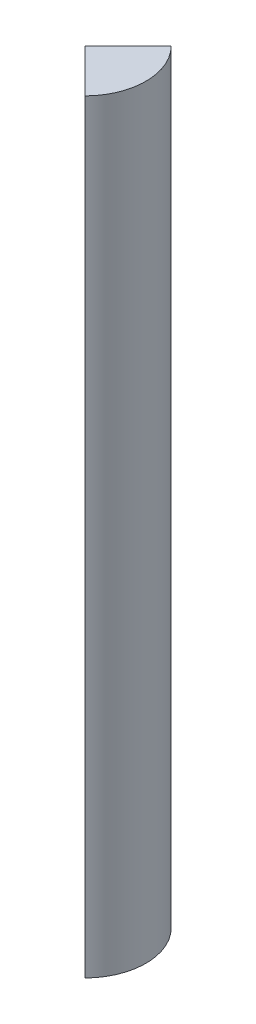
SolidWorks part; units mm, degrees
other "Markup1"
sketch "Sketch12"
ref_plane "Front Plane" through (0, 0, 0) normal (1, 0, 0) x (0, 1, 0)
ref_plane "Top Plane" through (0, 0, 0) normal (0, 0, 1) x (0, 1, 0)
ref_plane "Right Plane" through (0, 0, 0) normal (0, 1, 0) x (-1, 0, 0)
sketch "Sketch2" plane through (0, 0, 0) normal (1, 0, 0) x (0, 1, 0)
  line L0 (0, 0) -> (762, 0) construction
  line L1 (762, 0) -> (762, 78.359) construction
  line L2 (762, 78.359) -> (762, 76.2)
  line L3 (3.4018, 0) -> (0, 0)
  spline S0 degree 4 poles (0, 0) (0.0023, 0.0105) (0.0086, 0.031) (0.0277, 0.0698) (0.0612, 0.1247) (0.1053, 0.1858) (0.1923, 0.2927) (0.3229, 0.4308) (0.4903, 0.5871) (0.695, 0.7599) (0.9129, 0.9313) (1.1432, 1.102) (1.5318, 1.3747) (2.2426, 1.8346) (3.5248, 2.5796) (5.9038, 3.7977) (10.1506, 5.6937) (17.4785, 8.5235) (29.8706, 12.6463) (49.7755, 18.3188) (79.4252, 25.5145) (117.5433, 33.3386) (161.8994, 41.077) (209.5287, 48.1681) (257.2931, 54.2742) (305.159, 59.5209) (353.1026, 63.9965) (401.1066, 67.7665) (449.1572, 70.8839) (497.2431, 73.3933) (545.3551, 75.337) (593.4853, 76.7561) (641.627, 77.698) (689.7749, 78.217) (725.8875, 78.3488) (749.9625, 78.359) (762, 78.359) knots 0 0 0 0 0 0.000056 0.000112 0.000223 0.000335 0.000447 0.000828 0.00121 0.001524 0.001839 0.002269 0.002699 0.003991 0.006237 0.009973 0.016584 0.028152 0.047047 0.077827 0.124124 0.186686 0.249249 0.311812 0.374374 0.436937 0.4995 0.562062 0.624625 0.687187 0.74975 0.812312 0.874875 0.937438 1 1 1 1 1 construction
  spline S1 degree 4 poles (0, 0) (0.0023, 0.0105) (0.0086, 0.031) (0.0277, 0.0698) (0.0612, 0.1247) (0.1053, 0.1858) (0.1923, 0.2927) (0.3229, 0.4308) (0.4903, 0.5871) (0.695, 0.7599) (0.9129, 0.9313) (1.1432, 1.102) (1.5318, 1.3747) (2.2426, 1.8346) (3.5248, 2.5796) (5.9038, 3.7977) (10.1506, 5.6937) (17.4785, 8.5235) (29.8706, 12.6463) (49.7755, 18.3188) (79.4252, 25.5145) (117.5433, 33.3386) (161.8994, 41.077) (209.5287, 48.1681) (257.2931, 54.2742) (305.159, 59.5209) (353.1026, 63.9965) (401.1066, 67.7665) (449.1572, 70.8839) (497.2431, 73.3933) (545.3551, 75.337) (593.4853, 76.7561) (641.627, 77.698) (689.7749, 78.217) (725.8875, 78.3488) (749.9625, 78.359) (762, 78.359) knots 0 0 0 0 0 0.000056 0.000112 0.000223 0.000335 0.000447 0.000828 0.00121 0.001524 0.001839 0.002269 0.002699 0.003991 0.006237 0.009973 0.016584 0.028152 0.047047 0.077827 0.124124 0.186686 0.249249 0.311812 0.374374 0.436937 0.4995 0.562062 0.624625 0.687187 0.74975 0.812312 0.874875 0.937438 1 1 1 1 1
  spline S2 degree 1 poles (1.8679, -1.0827) (762, 76.2) knots 0 0 1 1 construction
  spline S3 degree 3 poles (1.8679, -1.0827) (1.9227, -1.0307) (2.0262, -0.9405) (2.3297, -0.7011) (2.7367, -0.4169) (3.1827, -0.1323) (3.5725, 0.1036) (4.1963, 0.4671) (5.1592, 0.9878) (6.879, 1.8455) (9.0976, 2.8537) (12.725, 4.3663) (17.3507, 6.113) (22.981, 8.0553) (28.6626, 9.8797) (36.2888, 12.1887) (45.8901, 14.8818) (57.4863, 17.8837) (69.1347, 20.7008) (80.8252, 23.3612) (96.4567, 26.7299) (116.0643, 30.6435) (139.6744, 34.9497) (163.347, 38.9211) (187.0706, 42.5955) (210.8364, 46.0019) (242.5718, 50.2157) (282.3174, 54.9128) (330.1041, 59.7424) (377.962, 63.8395) (425.875, 67.262) (489.8157, 70.9904) (569.8224, 74.1892) (665.8918, 76.035) (729.9659, 76.2) (762, 76.2) knots 0.000806 0.000806 0.000806 0.000806 0.001294 0.001782 0.002757 0.003609 0.004097 0.004709 0.00666 0.008612 0.012515 0.016418 0.024224 0.032031 0.039837 0.047643 0.063255 0.078868 0.09448 0.110093 0.125705 0.15693 0.188155 0.219379 0.250604 0.281829 0.313054 0.375504 0.437953 0.500403 0.562853 0.625302 0.750201 0.875101 1 1 1 1 only from (3.4018, 0) to (762, 76.2)
  dimension "D1" = 2.159
sketch "Sketch4" plane through (0, 0, 0) normal (1, 0, 0) x (0, 1, 0)
  line L0 (0, 0) -> (762, 0)
  line L1 (762, 0) -> (762, 78.359)
  spline S0 degree 4 poles (-2870.5736, 769.8211) (68.5769, -19.0817) (0.1375, -1.5402) (-0.2978, -0.4636) (0.0612, 0.1247) (0.1053, 0.1858) (0.1923, 0.2927) (0.3229, 0.4308) (0.4903, 0.5871) (0.695, 0.7599) (0.9129, 0.9313) (1.1432, 1.102) (1.5318, 1.3747) (2.2426, 1.8346) (3.5248, 2.5796) (5.9038, 3.7977) (10.1506, 5.6937) (17.4785, 8.5235) (29.8706, 12.6463) (49.7755, 18.3188) (79.4252, 25.5145) (117.5433, 33.3386) (161.8994, 41.077) (209.5287, 48.1681) (257.2931, 54.2742) (305.159, 59.5209) (353.1026, 63.9965) (401.1066, 67.7665) (449.1572, 70.8839) (497.2431, 73.3933) (545.3551, 75.337) (593.4853, 76.7561) (641.627, 77.698) (949.2491, 81.0136) (1244.9482, 66.9537) (1527.4922, 97.6231) (1819.2843, 2734.4842) knots -0.003249 -0.003249 -0.003249 -0.003249 -0.003249 0.000056 0.000112 0.000223 0.000335 0.000447 0.000828 0.00121 0.001524 0.001839 0.002269 0.002699 0.003991 0.006237 0.009973 0.016584 0.028152 0.047047 0.077827 0.124124 0.186686 0.249249 0.311812 0.374374 0.436937 0.4995 0.562062 0.624625 0.687187 0.74975 0.812312 0.874875 0.937438 2.348626 2.348626 2.348626 2.348626 2.348626 only from (0, 0) to (762, 78.359) construction
  spline S1 degree 4 poles (0, 0) (0.0023, 0.0105) (0.0086, 0.031) (0.0277, 0.0698) (0.0612, 0.1247) (0.1053, 0.1858) (0.1923, 0.2927) (0.3229, 0.4308) (0.4903, 0.5871) (0.695, 0.7599) (0.9129, 0.9313) (1.1432, 1.102) (1.5318, 1.3747) (2.2426, 1.8346) (3.5248, 2.5796) (5.9038, 3.7977) (10.1506, 5.6937) (17.4785, 8.5235) (29.8706, 12.6463) (49.7755, 18.3188) (79.4252, 25.5145) (117.5433, 33.3386) (161.8994, 41.077) (209.5287, 48.1681) (257.2931, 54.2742) (305.159, 59.5209) (353.1026, 63.9965) (401.1066, 67.7665) (449.1572, 70.8839) (497.2431, 73.3933) (545.3551, 75.337) (593.4853, 76.7561) (641.627, 77.698) (689.7749, 78.217) (725.8875, 78.3488) (749.9625, 78.359) (762, 78.359) knots 0 0 0 0 0 0.000056 0.000112 0.000223 0.000335 0.000447 0.000828 0.00121 0.001524 0.001839 0.002269 0.002699 0.003991 0.006237 0.009973 0.016584 0.028152 0.047047 0.077827 0.124124 0.186686 0.249249 0.311812 0.374374 0.436937 0.4995 0.562062 0.624625 0.687187 0.74975 0.812312 0.874875 0.937438 1 1 1 1 1
revolve "Revolve1" add sketch "Sketch4" angle 360 about L0 region at (0, 454.2197, 32.884)
sketch "Sketch5" plane through (0, 762, 0) normal (0, 1, 0) x (-1, 0, 0)
  circle A1 centre (0, 0) radius 78.359
  circle A2 centre (0, 0) radius 78.359
  dimension "D1" = 0
extrude "Boss-Extrude1" add sketch "Sketch5" along normal blind 1117.6
ref_axis "Axis1" through (0, 1879.6, 0) along (0, -1, 0)
sketch "Sketch10" plane through (0, 1879.6, 0) normal (0, 1, 0) x (-1, 0, 0)
  line L1 (0, 0) -> (-78.359, 0) construction
  line L3 (-55.4082, 55.4082) -> (0, 0)
  line L4 (0, 0) -> (-55.4082, -55.4082)
  circle A0 centre (0, 0) radius 78.359 construction
  circle A2 centre (0, 0) radius 78.359
  arc A3 (-55.4082, -55.4082) -> (-55.4082, 55.4082) centre (0, 0) ccw
  dimension "D1" = 45
  dimension "D2" = 0
extrude "Cut-Extrude2" cut sketch "Sketch10" against normal through all
ref_plane "Plane2" through (0, 1371.6, 0) normal (0, 1, 0) x (1, 0, 0)
ref_axis "Axis2" through (86.1949, 1371.6, 0) along (-1, 0, 0)
ref_plane "Plane3" through (0, 0, 0) normal (0, 0, 1) x (-1, 0, 0)
sketch "Sketch14" plane through (0, 0, 0) normal (0, 0, 1) x (-1, 0, 0)
  line L0 (-78.359, -1219.2) -> (-78.359, -1524)
  line L1 (-78.359, -762) -> (-78.359, -1879.6) construction
  line L2 (-78.359, -1524) -> (-261.239, -1499.9043)
  line L3 (-261.239, -1499.9043) -> (-261.239, -1459.2643)
  line L4 (-261.239, -1459.2643) -> (-78.359, -1219.2)
  line L6 (-78.359, -1219.2) -> (-55.4082, -1189.0727)
  line L7 (-78.359, -1219.2) -> (-52.959, -1219.2)
  line L8 (-78.359, -1219.2) -> (-78.359, -1524)
  line L9 (-78.359, -1524) -> (-52.959, -1524)
  line L10 (-52.959, -1219.2) -> (-52.959, -1524)
  line L11 (-55.4082, -762) -> (-55.4082, -1879.6) construction
  line L12 (-55.4082, -1189.0727) -> (-55.4082, -1527.0239)
  line L13 (-78.359, -1524) -> (-55.4082, -1527.0239)
  point P10 (-52.959, -1371.6)
  dimension "D1" = 304.8
  dimension "D2" = 40.64
  dimension "D3" = 182.88
  dimension "D4" = 37.3
  dimension "D5" = 508
  dimension "D6" = 25.4
  dimension "D7" = 1189.0727
extrude "Boss-Extrude3" add sketch "Sketch14" along normal mid plane 2.54 contours L12 L6 L7 | L9 L13 L12 | L4 L0 L2 L3 | L8 L7 L10 L9 region at (63.0585, 1209.1576, 0) region at (63.0585, 1525.008, 0)
sketch "Sketch15" plane through (0, 1879.6, 0) normal (0, 1, 0) x (-1, 0, 0)
  line L0 (0, 0) -> (-718.4205, 718.4205)
  line L1 (-55.4082, 55.4082) -> (0, 0) construction
  line L2 (0, 0) -> (-718.4205, -718.4205)
  line L3 (0, 0) -> (-55.4082, -55.4082) construction
  arc A0 (-718.4205, -718.4205) -> (-718.4205, 718.4205) centre (0, 0) cw
  line M3 (-55.4082, -55.4082) -> (0, 0)
  line M4 (0, 0) -> (-55.4082, 55.4082)
  arc M5 (-55.4082, 55.4082) -> (-55.4082, -55.4082) centre (0, 0) ccw
  dimension "D1" = 1016
extrude "Boss-Extrude4" add sketch "Sketch15" along normal blind 7620 and the other way blind 5080 separate body contours A0 L2 L0 M5 | M5 M3 M4 region at (47.0319, 1879.6, 0) region at (613.1819, 1879.6, 0)
combine bodies "Combine1" operation type subtract main body 134 bodies to subtract 133
sketch "Sketch16" plane through (0, 0, 0) normal (0, 0, 1) x (-1, 0, 0)
  point P0 (-160, -500)
  dimension "D1" = 500
  dimension "D2" = 160
equation "\"degree\"= 12.5"
equation "\"angle\"= 12.5"
equation "\"D15@Sketch13\"=\"angle\""
